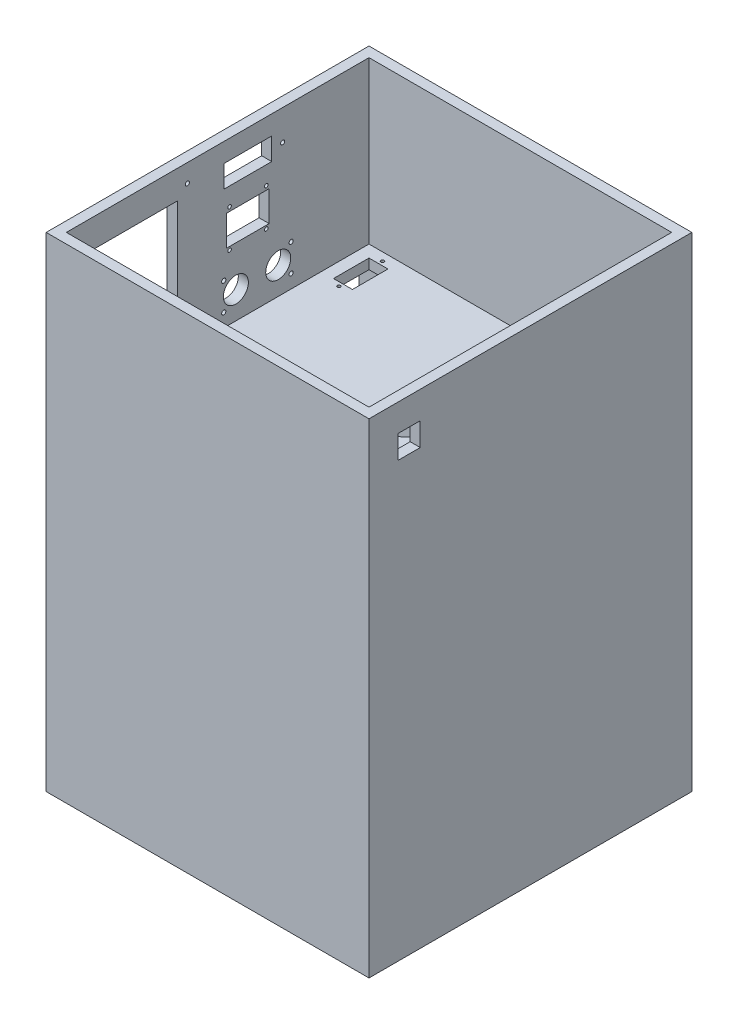
SolidWorks part; units mm, degrees
ref_plane "Front Plane" through (0, 0, 0) normal (0, 0, 1) x (1, 0, 0)
ref_plane "Top Plane" through (0, 0, 0) normal (0, 1, 0) x (1, 0, 0)
ref_plane "Right Plane" through (0, 0, 0) normal (1, 0, 0) x (0, 0, -1)
sketch "Sketch1" plane through (0, 0, 0) normal (0, 0, 1) x (1, 0, 0)
  line L1 (-101.6, -101.6) -> (101.6, -101.6)
  line L2 (-101.6, -101.6) -> (-101.6, 101.6)
  line L3 (-101.6, 101.6) -> (101.6, 101.6)
  line L4 (101.6, -101.6) -> (101.6, 101.6)
  line L5 (-101.6, -101.6) -> (101.6, 101.6) construction
  line L6 (-101.6, 101.6) -> (101.6, -101.6) construction
  line L11 (-94.7622, -94.7622) -> (94.7622, 94.7622) construction
  line L12 (-94.7622, 94.7622) -> (94.7622, -94.7622) construction
  point P0 (0, 0)
  point P6 (0, 0)
  dimension "D1" = 203.2
  dimension "D2" = 203.2
extrude "Boss-Extrude1" add sketch "Sketch1" along normal blind 203.2
sketch "Sketch2" plane through (-101.6, 0, 0) normal (-1, 0, 0) x (0, 0, 1)
  point P10 (101.6, 0)
shell "Shell1" thickness 6.35 removed face at (-101.6, 0, 101.6)
sketch "Sketch4" plane through (0, 101.6, 0) normal (0, 1, 0) x (1, 0, 0)
  line L0 (101.6, -203.2) -> (101.6, 0) construction
  line L1 (-101.6, 0) -> (101.6, 0)
  line L2 (-101.6, 0) -> (-101.6, -203.2)
  line L3 (-101.6, -203.2) -> (101.6, -203.2)
  line L4 (101.6, 0) -> (101.6, -203.2)
  line L5 (-101.6, 0) -> (101.6, -203.2) construction
  line L6 (-101.6, -203.2) -> (101.6, 0) construction
  line L7 (101.6, 0) -> (-101.6, 0) construction
  point P0 (0, -101.6)
  dimension "D1" = 203.2
  dimension "D2" = 203.2
  dimension "D3" = 101.6
  dimension "D4" = 101.6
extrude "Boss-Extrude2" add sketch "Sketch4" along normal blind 101.6
shell "Shell2" thickness 6.35 removed face at (0, 203.2, 101.6)
sketch "Sketch5" plane through (-101.6, 0, 0) normal (-1, 0, 0) x (0, 0, 1)
  line L0 (196.85, 101.6) -> (6.35, 101.6) construction
  line L1 (196.85, 101.6) -> (6.35, 101.6)
  line L2 (63.4744, 133.458) -> (63.4744, 104.6205) construction
  line L5 (203.2, 203.2) -> (203.2, -101.6) construction
  line L6 (69.215, 144.1729) -> (95.885, 144.1729)
  line L7 (69.215, 144.1729) -> (69.215, 163.2229)
  line L8 (69.215, 163.2229) -> (95.885, 163.2229)
  line L9 (95.885, 144.1729) -> (95.885, 163.2229)
  line L10 (69.215, 144.1729) -> (95.885, 163.2229) construction
  line L11 (69.215, 163.2229) -> (95.885, 144.1729) construction
  line L12 (67.564, 191.135) -> (97.536, 191.135)
  line L13 (67.564, 191.135) -> (67.564, 177.165)
  line L14 (67.564, 177.165) -> (97.536, 177.165)
  line L15 (97.536, 191.135) -> (97.536, 177.165)
  line L16 (67.564, 191.135) -> (97.536, 177.165) construction
  line L17 (67.564, 177.165) -> (97.536, 191.135) construction
  line L23 (0, 203.2) -> (203.2, 203.2) construction
  line L35 (55.3464, 118.6599) -> (115.145, 118.6599) construction
  line L36 (190.5, 116.84) -> (127, 116.84)
  line L37 (190.5, 116.84) -> (190.5, 185.42)
  line L38 (190.5, 185.42) -> (127, 185.42)
  line L39 (127, 116.84) -> (127, 185.42)
  line L40 (190.5, 116.84) -> (127, 185.42) construction
  line L41 (190.5, 185.42) -> (127, 116.84) construction
  line L44 (0, 203.2) -> (0, -101.6) construction
  line L45 (82.55, 133.6586) -> (82.55, 180.2268) construction
  line L46 (58.1837, 153.6979) -> (103.1417, 153.6979) construction
  circle A10 centre (63.4744, 118.6671) radius 7.874
  circle A11 centre (90.1444, 118.6671) radius 7.874
  circle A12 centre (55.3464, 127.2959) radius 1.32
  circle A13 centre (97.7644, 127.2959) radius 1.32
  circle A14 centre (97.7644, 110.0239) radius 1.32
  circle A15 centre (55.3464, 110.0239) radius 1.32
  circle A16 centre (70.993, 165.7629) radius 1.143
  circle A17 centre (94.107, 165.7629) radius 1.143
  circle A20 centre (68.013, 142.1409) radius 1.143 [skipped]
  circle A21 centre (91.127, 142.1409) radius 1.143 [skipped]
  circle A22 centre (70.993, 142.1409) radius 1.143
  circle A23 centre (94.107, 142.1409) radius 1.143
  circle A24 centre (120.65, 191.77) radius 1.27
  circle A25 centre (196.85, 191.77) radius 1.27
  circle A26 centre (196.85, 109.22) radius 1.27
  circle A27 centre (120.65, 109.22) radius 1.27
  circle A28 centre (60.706, 184.15) radius 1.27
  point P9 (82.55, 153.6979)
  point P14 (82.55, 184.15)
  point P19 (158.75, 151.13)
  dimension "D2" = 15.748
  dimension "D11" = 2.286
  dimension "D3" = 82.55
  dimension "D12" = 1.778
  dimension "D23" = 2.54
  dimension "D27" = 2.54
  dimension "D28" = 6.858
  dimension "D6" = 8.636
  dimension "D7" = 8.128
  dimension "D9" = 26.67
  dimension "D10" = 19.05
  dimension "D13" = 2.54
  dimension "D14" = 29.972
  dimension "D15" = 13.97
  dimension "D16" = 19.05
  dimension "D17" = 63.5
  dimension "D18" = 68.58
  dimension "D19" = 15.24
  dimension "D20" = 12.7
  dimension "D21" = 82.55
  dimension "D22" = 17.78
  dimension "D24" = 6.35
  dimension "D25" = 6.35
  dimension "D26" = 7.62
  dimension "D8" = 2
  dimension "D4" = 2
  dimension "D5" = 2
extrude "Cut-Extrude1" cut sketch "Sketch5" against normal up to surface (6.35 mm away) contours A14 | A12 | A22 | L37 L36 L39 L38 | L7 L6 L9 L8 | L13 L12 L15 L14 | A10 | A11 | A13 | A23 | A27 | A24 | A25 | A26 | A16 | A17 | A15 | A28 region at (-101.6, 127.2959, 55.3464) region at (-101.6, 110.0239, 97.7644) region at (-101.6, 142.1409, 70.993)
sketch "Sketch6" plane through (0, 101.6, 0) normal (0, 1, 0) x (1, 0, 0)
  line L0 (11.7832, -118.3918) -> (11.7832, -172.3668)
  line L2 (-95.25, -196.85) -> (-8.4224, -110.0224) construction
  line L3 (95.25, -196.85) -> (-95.25, -6.35) construction
  line L7 (-8.4224, -110.0224) -> (-46.5885, -148.1885)
  line L8 (11.7832, -89.8168) -> (95.25, -6.35) construction
  line L9 (11.7832, -89.8168) -> (11.7832, -49.2908) construction
  line L10 (22.7236, -98.7068) -> (29.5632, -98.7068)
  line L12 (22.7236, -80.9268) -> (29.5632, -80.9268)
  line L13 (29.5632, -98.7068) -> (29.5632, -80.9268)
  line L14 (-0.8256, -96.1212) -> (11.7832, -89.8168) construction
  line L15 (-0.8256, -83.5124) -> (11.7832, -89.8168) construction
  line L16 (-95.25, -6.35) -> (-95.25, -196.85) construction
  line L17 (-87.63, -13.97) -> (-75.692, -13.97)
  line L18 (-87.63, -13.97) -> (-87.63, -36.322)
  line L19 (-87.63, -36.322) -> (-75.692, -36.322)
  line L20 (-75.692, -13.97) -> (-75.692, -36.322)
  line L21 (95.25, -6.35) -> (-95.25, -6.35) construction
  line L22 (-81.661, -36.322) -> (-81.661, -8.492) construction
  line L23 (-76.5374, -133.6698) -> (-64.5994, -133.6698)
  line L24 (-76.5374, -133.6698) -> (-76.5374, -156.0218)
  line L25 (-76.5374, -156.0218) -> (-64.5994, -156.0218)
  line L26 (-64.5994, -133.6698) -> (-64.5994, -156.0218)
  line L27 (-70.5684, -156.0218) -> (-70.5684, -160.8997) construction
  circle A9 centre (24.4832, -126.0832) radius 3.175
  arc A15 (-46.5885, -148.1885) -> (11.7832, -172.3668) centre (11.7832, -89.8168) ccw
  arc A16 (-8.4224, -110.0224) -> (11.7832, -118.3918) centre (11.7832, -89.8168) ccw
  arc A17 (22.7236, -80.9268) -> (22.7236, -98.7068) centre (11.7832, -89.8168) ccw
  circle A18 centre (11.7832, -72.5448) radius 2.0955
  circle A19 centre (11.7832, -107.3428) radius 2.0955
  circle A20 centre (-81.661, -11.43) radius 1.016
  circle A21 centre (-81.661, -38.862) radius 1.016
  circle A22 centre (-70.5684, -131.1298) radius 1.016
  circle A24 centre (-70.5684, -158.5618) radius 1.016
  point P38 (-81.661, -13.97)
  point P49 (-70.5684, -133.6698)
  dimension "D2" = 165.1
  dimension "D3" = 57.15
  dimension "D4" = 28.194
  dimension "D7" = 4.191
  dimension "D9" = 6.35
  dimension "D16" = 2.032
  dimension "D5" = 17.78
  dimension "D6" = 17.78
  dimension "D8" = 17.272
  dimension "D10" = 12.7
  dimension "D11" = 53.975
  dimension "D12" = 22.352
  dimension "D13" = 11.938
  dimension "D14" = 7.62
  dimension "D15" = 7.62
  dimension "D17" = 2.54
  dimension "D18" = 2.54
  dimension "D19" = 2.54
extrude "Cut-Extrude2" cut sketch "Sketch6" against normal up to surface (6.35 mm away) up to face at (-3.175, 95.25, 101.6)
sketch "Sketch8" plane through (0, -101.6, 0) normal (0, -1, 0) x (1, 0, 0)
  circle A2 centre (-89.4934, 190.6084) radius 3.3544
  circle A3 centre (88.3066, 190.6084) radius 3.3544
  circle A4 centre (88.3066, 12.8084) radius 3.3544
  circle A5 centre (-89.4934, 12.8084) radius 3.3544
  dimension "D1" = 2
  dimension "D2" = 2
extrude "Cut-Extrude3" cut sketch "Sketch8" against normal up to surface (6.35 mm away) contours A3 | A2 | A4 | A5 region at (88.3066, -101.6, 190.6084) up to face at (-3.175, -95.25, 101.6)
sketch "Sketch9" plane through (101.6, 0, 0) normal (1, 0, 0) x (0, 0, -1)
  line L0 (-196.85, 101.6) -> (-6.35, 101.6) construction
  line L1 (-196.85, 101.6) -> (-6.35, 101.6)
  line L3 (-184.9664, 186.0509) -> (-170.9467, 186.0509)
  line L4 (-184.9664, 186.0509) -> (-184.9664, 171.4108)
  line L5 (-184.9664, 171.4108) -> (-170.9467, 171.4108)
  line L6 (-170.9467, 186.0509) -> (-170.9467, 171.4108)
  line L7 (-184.9664, 186.0509) -> (-170.9467, 171.4108) construction
  line L8 (-184.9664, 171.4108) -> (-170.9467, 186.0509) construction
  point P2 (-177.9566, 178.7309)
extrude "Cut-Extrude4" cut sketch "Sketch9" along direction (-1, 0, 0) on the side against the normal up to surface (6.35 mm away) contours L4 L3 L6 L5 up to face at (95.25, 152.4, 101.6)
